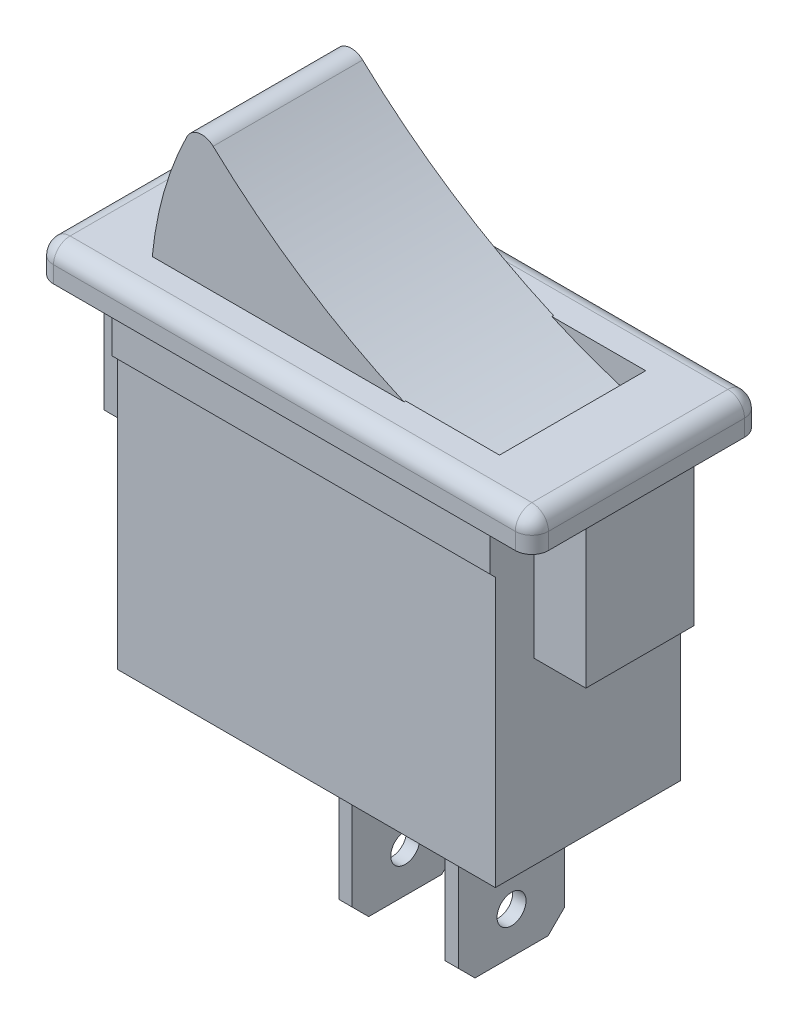
SolidWorks part; units mm, degrees
ref_plane "Front Plane" through (0, 0, 0) normal (0, 0, 1) x (1, 0, 0)
ref_plane "Top Plane" through (0, 0, 0) normal (0, 1, 0) x (1, 0, 0)
ref_plane "Right Plane" through (0, 0, 0) normal (1, 0, 0) x (0, 0, -1)
sketch "Sketch1" plane through (0, 0, 0) normal (0, 1, 0) x (1, 0, 0)
  line L1 (-11.375, -5.575) -> (11.375, -5.575)
  line L2 (-11.375, -5.575) -> (-11.375, 5.575)
  line L3 (-11.375, 5.575) -> (11.375, 5.575)
  line L4 (11.375, -5.575) -> (11.375, 5.575)
  line L5 (-11.375, -5.575) -> (11.375, 5.575) construction
  line L6 (-11.375, 5.575) -> (11.375, -5.575) construction
  point P0 (0, 0)
  dimension "D1" = 22.75
  dimension "D2" = 11.15
extrude "Boss-Extrude1" add sketch "Sketch1" along normal blind 19.5
sketch "Sketch2" plane through (0, 19.5, 0) normal (0, 1, 0) x (1, 0, 0)
  line L1 (-10.45, -4.4) -> (10.45, -4.4)
  line L2 (-10.45, -4.4) -> (-10.45, 4.4)
  line L3 (-10.45, 4.4) -> (10.45, 4.4)
  line L4 (10.45, -4.4) -> (10.45, 4.4)
  line L5 (-10.45, -4.4) -> (10.45, 4.4) construction
  line L6 (-10.45, 4.4) -> (10.45, -4.4) construction
  line L7 (-14.9, -6.9) -> (14.9, -6.9)
  line L8 (-14.9, -6.9) -> (-14.9, 6.9)
  line L9 (-14.9, 6.9) -> (14.9, 6.9)
  line L10 (14.9, -6.9) -> (14.9, 6.9)
  line L11 (-14.9, -6.9) -> (14.9, 6.9) construction
  line L12 (-14.9, 6.9) -> (14.9, -6.9) construction
  point P0 (0, 0)
  point P6 (0, 0)
  dimension "D1" = 29.8
  dimension "D2" = 13.8
  dimension "D3" = 20.9
  dimension "D4" = 8.8
extrude "Boss-Extrude2" add sketch "Sketch2" along normal blind 2
fillet "Fillet1" radius 1 8 edges at (-14.9, 20.5, 6.9) (-14.9, 20.5, -6.9) (14.9, 20.5, -6.9) (14.9, 20.5, 6.9) (14.9, 21.5, 0) (0, 21.5, -6.9) (0, 21.5, 6.9) (-14.9, 21.5, 0)
sketch "Sketch3" plane through (0, 0, 0) normal (0, 0, 1) x (1, 0, 0)
  line L0 (-10.45, 19.5) -> (10.45, 19.5)
  circle A0 centre (10.45, 19.5) radius 20.9
  circle A1 centre (21.2388, 58.9282) radius 40.8776
extrude "Boss-Extrude3" add sketch "Sketch3" along normal mid plane 9 contours A1 A0 L0 region at (-3.6411, 22.8415, 0)
fillet "Fillet2" radius 1 1 edges at (-7.6289, 29.9863, 0)
sketch "Sketch4" plane through (0, 0, 0) normal (0, -1, 0) x (-1, 0, 0)
  line L0 (-16.39, 0) -> (16.39, 0) construction
  line L1 (-5.975, 3.2) -> (-6.775, 3.2)
  line L2 (-5.975, 3.2) -> (-5.975, -3.2)
  line L3 (-5.975, -3.2) -> (-6.775, -3.2)
  line L4 (-6.775, 3.2) -> (-6.775, -3.2)
  line L5 (-5.975, 3.2) -> (-6.775, -3.2) construction
  line L6 (-5.975, -3.2) -> (-6.775, 3.2) construction
  line L7 (-11.375, -5.575) -> (-11.375, 5.575) construction
  line L8 (0.425, 3.2) -> (-0.375, 3.2)
  line L9 (0.425, 3.2) -> (0.425, -3.2)
  line L10 (0.425, -3.2) -> (-0.375, -3.2)
  line L11 (-0.375, 3.2) -> (-0.375, -3.2)
  line L12 (0.425, 3.2) -> (-0.375, -3.2) construction
  line L13 (0.425, -3.2) -> (-0.375, 3.2) construction
  point P0 (-6.375, 0)
  point P7 (0.025, 0)
  dimension "D1" = 4.6
  dimension "D2" = 7.2
  dimension "D3" = 0.8
  dimension "D4" = 6.4
extrude "Boss-Extrude4" add sketch "Sketch4" along normal blind 8.7
chamfer "Chamfer1" distance 1 angle 45 4 edges at (-0.025, -8.7, -3.2) (6.375, -8.7, -3.2) (6.375, -8.7, 3.2) (-0.025, -8.7, 3.2)
sketch "Sketch5" plane through (0, 19.5, 0) normal (0, -1, 0) x (1, 0, 0)
  line L1 (-14.5, -3.25) -> (14.5, -3.25)
  line L2 (-14.5, -3.25) -> (-14.5, 3.25)
  line L3 (-14.5, 3.25) -> (14.5, 3.25)
  line L4 (14.5, -3.25) -> (14.5, 3.25)
  line L5 (-14.5, -3.25) -> (14.5, 3.25) construction
  line L6 (-14.5, 3.25) -> (14.5, -3.25) construction
  point P0 (0, 0)
  dimension "D1" = 29
  dimension "D2" = 6.5
extrude "Boss-Extrude5" add sketch "Sketch5" along normal blind 8.7
sketch "Sketch6" plane through (0, 19.5, 0) normal (0, -1, 0) x (1, 0, 0)
  line L0 (-11.375, 3.25) -> (-11.375, 5.575) construction
  line L1 (-11.375, -5.89) -> (11.375, -5.89)
  line L2 (-11.375, -5.89) -> (-11.375, 5.89)
  line L3 (-11.375, 5.89) -> (11.375, 5.89)
  line L4 (11.375, -5.89) -> (11.375, 5.89)
  line L5 (-11.375, -5.89) -> (11.375, 5.89) construction
  line L6 (-11.375, 5.89) -> (11.375, -5.89) construction
  point P0 (0, 0)
  dimension "D1" = 11.78
extrude "Boss-Extrude6" add sketch "Sketch6" along normal blind 3.5
chamfer "Chamfer2" distance 0.5 angle 45 2 edges at (0, 16, -5.89) (0, 16, 5.89)
sketch "Sketch7" plane through (-0.425, 0, 0) normal (-1, 0, 0) x (0, 0, 1)
  line L0 (0, -16.39) -> (0, 16.39) construction
  circle A0 centre (0, -6.2041) radius 0.8717
extrude "Cut-Extrude1" cut sketch "Sketch7" against normal through all both and the other way through all
